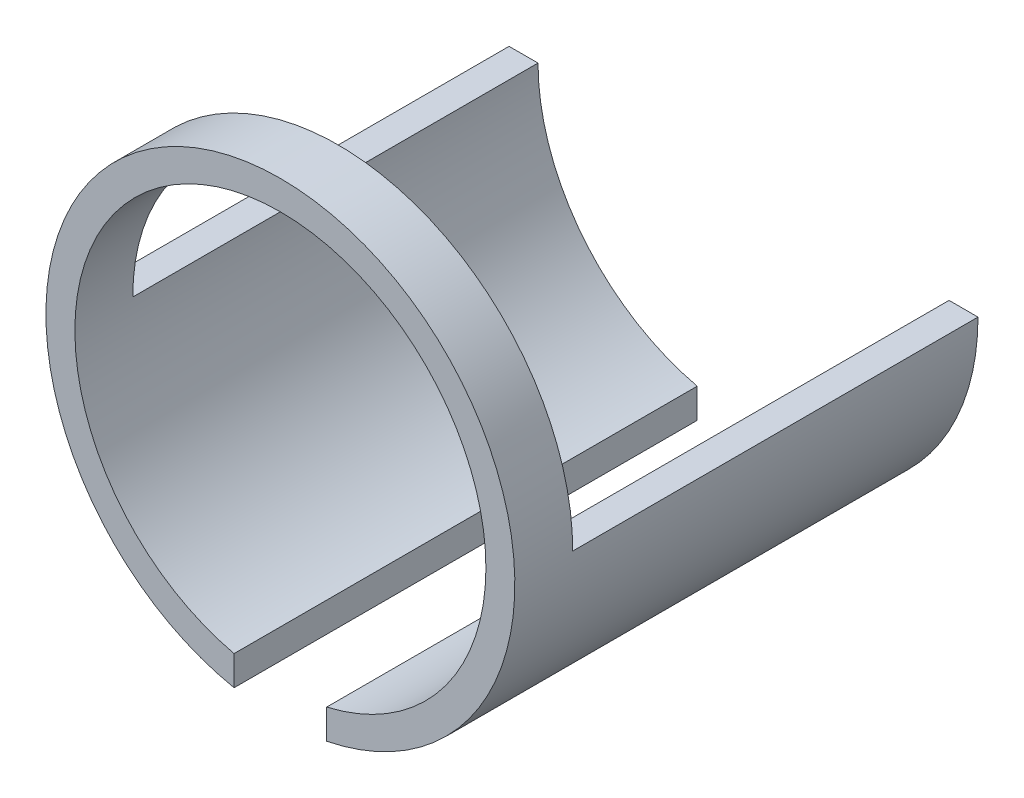
SolidWorks part; units mm, degrees
ref_plane "前基準面" through (0, 0, 0) normal (0, 0, 1) x (1, 0, 0)
ref_plane "上基準面" through (0, 0, 0) normal (0, 1, 0) x (1, 0, 0)
ref_plane "右基準面" through (0, 0, 0) normal (1, 0, 0) x (0, 0, -1)
sketch "草圖2" plane through (0, 0, 0) normal (0, 0, 1) x (1, 0, 0)
  circle A0 centre (0, 0) radius 35.5
  circle A1 centre (0, 0) radius 40.5
  dimension "D1" = 71
  dimension "D2" = 5
extrude "填料-伸長1" add sketch "草圖2" against normal blind 80
sketch "草圖3" plane through (0, 0, 0) normal (0, 0, 1) x (1, 0, 0)
  line L0 (0, 0) -> (0, -40.5) construction
  line L1 (8, -34.5868) -> (8, -39.702)
  line L2 (-8, -34.5868) -> (-8, -39.702)
  circle A0 centre (0, 0) radius 40.5 construction
  circle A1 centre (0, 0) radius 35.5 construction
  arc A2 (-8, -34.5868) -> (8, -34.5868) centre (0, 0) ccw
  arc A3 (-8, -39.702) -> (8, -39.702) centre (0, 0) ccw
  dimension "D1" = 16
extrude "除料-伸長1" cut sketch "草圖3" against normal through all
sketch "草圖4" plane through (0, 0, 0) normal (1, 0, 0) x (0, 0, -1)
  line L0 (10, 40.5) -> (10, 0)
  line L1 (80, 40.5) -> (0, 40.5) construction
  line L2 (10, 0) -> (80, 0)
  line L3 (80, -39.702) -> (80, 40.5) construction
  line L4 (80, 0) -> (80, 40.5)
  line L5 (80, 40.5) -> (10, 40.5)
  point P4 (10, 0)
  dimension "D1" = 70
extrude "除料-伸長2" cut sketch "草圖4" against normal through all both and the other way through all
